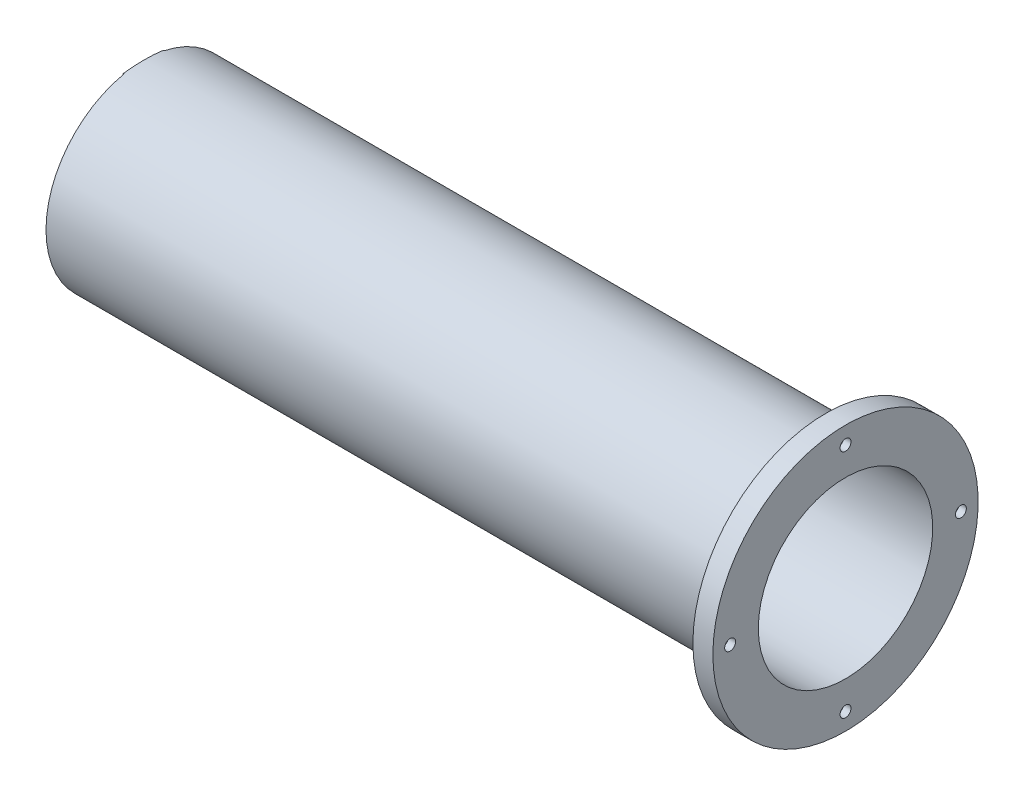
SolidWorks part; units mm, degrees
ref_plane "Plano frontal" through (0, 0, 0) normal (0, 0, 1) x (1, 0, 0)
ref_plane "Plano superior" through (0, 0, 0) normal (0, 1, 0) x (1, 0, 0)
ref_plane "Plano direito" through (0, 0, 0) normal (1, 0, 0) x (0, 0, -1)
ref_axis "eixo de revolução" through (-88.99, 0, 0) along (1, 0, 0)
sketch "Esboço1" plane through (0, 0, 0) normal (0, 0, 1) x (1, 0, 0)
  line L0 (-63.8345, 0) -> (-63.8345, 27)
  line L1 (-88.99, 0) -> (88.99, 0) construction
  line L4 (-63.8345, 27) -> (123.6655, 27)
  line L5 (-60.8345, 0) -> (-60.8345, 19)
  line L6 (-55.8345, 24) -> (129.1655, 24)
  line L7 (129.1655, 24) -> (129.1655, 36.5)
  line L8 (129.1655, 36.5) -> (123.6655, 36.5)
  line L9 (123.6655, 36.5) -> (123.6655, 27)
  line L10 (-63.8345, 0) -> (-60.8345, 0)
  arc A1 (-60.8345, 19) -> (-55.8345, 24) centre (-55.8345, 19) cw
  dimension "D6" = 5
  dimension "D8" = 7.854
  dimension "D1" = 27
  dimension "D4" = 3
  dimension "D5" = 3
  dimension "D7" = 19
  dimension "D9" = 190
  dimension "D10" = 12.5
  dimension "D11" = 5.5
revolve "revolução" add sketch "Esboço1" angle 360 about axis through (-88.99, 0, 0) along (1, 0, 0)
sketch "Esboço2" plane through (0, 0, 0) normal (0, 0, 1) x (1, 0, 0)
  line L1 (-73.8345, 0) -> (-63.8345, 0)
  line L2 (-63.8345, 27) -> (-63.8345, -27) construction
  line L3 (-73.8345, 0) -> (-63.8345, 27)
  line L4 (-63.8345, 27) -> (-63.8345, 0)
  line L5 (-63.8345, 0) -> (-63.8345, -27)
  line L6 (-63.8345, -27) -> (-73.8345, 0)
  circle A0 centre (-68.8345, 0) radius 2
  dimension "D3" = 4
  dimension "D1" = 0
  dimension "D2" = 10
extrude "Ressalto-extrusão1" add sketch "Esboço2" along normal mid plane 11 separate body contours A0 L1 L6 L5 | A0 L1 L4 L3 region at (-67.0865, 9.3979, 0) region at (-67.0865, -9.3979, 0)
sketch "Esboço3" plane through (-63.8345, 0, 0) normal (-1, 0, 0) x (0, 0, 1)
  circle A0 centre (0, 0) radius 33.5307
  circle A1 centre (0, 0) radius 27
  circle A2 centre (0, 0) radius 27
  dimension "D1" = 0
extrude "Corte-extrusão1" cut sketch "Esboço3" along normal blind 11
sketch "Esboço4" plane through (123.6655, 0, 0) normal (-1, 0, 0) x (0, 0, 1)
  line L0 (0, 27) -> (0, 36.5) construction
  circle A0 centre (0, 0) radius 27 construction
  circle A1 centre (0, 0) radius 36.5 construction
  circle A2 centre (0, 31.75) radius 3.25
  circle A3 centre (0, 31.75) radius 1.5
  dimension "D1" = 6.5
  dimension "D2" = 3
extrude "Corte-extrusão3" cut sketch "Esboço4" against normal blind 3.5 contours A2
extrude "Corte-extrusão4" cut sketch "Esboço4<3>" against normal through all contours A3 L0 | L0 A3 region at (123.6655, 31.75, -0.6366) region at (123.6655, 31.75, 0.6366)
sketch "Esboço4<3>" plane through (123.6655, 0, 0) normal (-1, 0, 0) x (0, 0, 1) same geometry as "Esboço4"
pattern_circular "PadrãoCircular7" count 4 every 90 about axis through (123.6655, 0, 0) along (-1, 0, 0) of "Corte-extrusão4", "Corte-extrusão3"
combine bodies "Combinar1" operation type add bodies to combine 107 103
